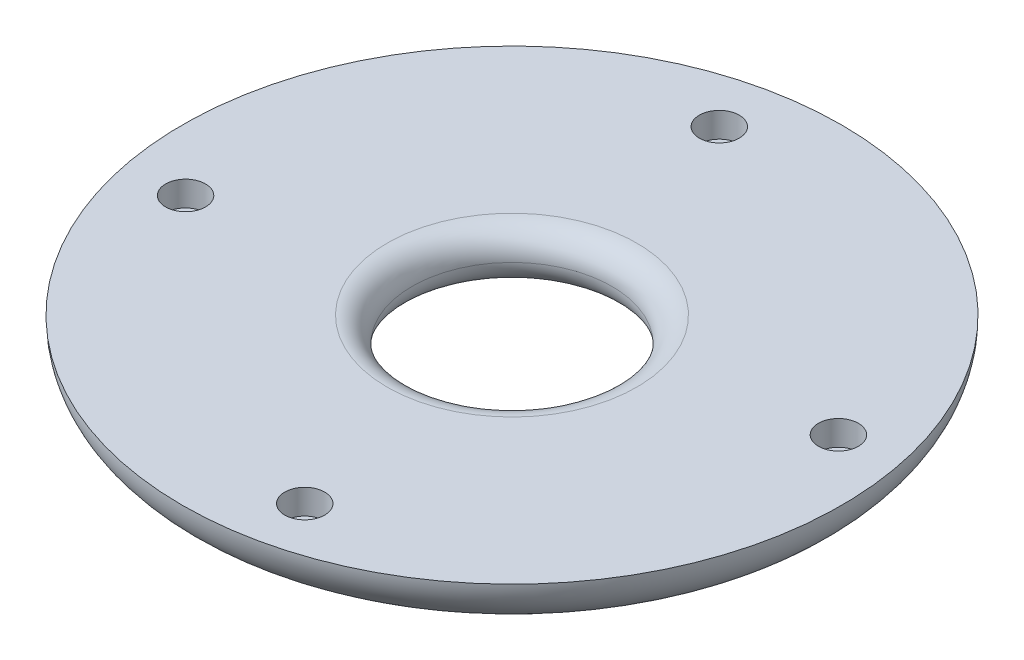
SolidWorks part; units mm, degrees
ref_plane "Front Plane" through (0, 0, 0) normal (0, 0, 1) x (1, 0, 0)
ref_plane "Top Plane" through (0, 0, 0) normal (0, 1, 0) x (1, 0, 0)
ref_plane "Right Plane" through (0, 0, 0) normal (1, 0, 0) x (0, 0, -1)
sketch "Sketch1" plane through (0, 0, 0) normal (0, 1, 0) x (1, 0, 0)
  circle A0 centre (0, 0) radius 33
extrude "Boss-Extrude1" add sketch "Sketch1" along normal blind 5
sketch "Sketch2" plane through (0, 5, 0) normal (0, 1, 0) x (1, 0, 0)
  circle A0 centre (-26.72, -5.9654) radius 2
  circle A1 centre (-5.9654, 26.72) radius 2
  circle A2 centre (26.72, 5.9654) radius 2
  circle A3 centre (5.9654, -26.72) radius 2
  point P11 (0, 0)
  dimension "D1" = 4
extrude "Cut-Extrude1" cut sketch "Sketch2" against normal blind 2.5
fillet "Fillet1" radius 5 1 edges at (0, 0, 33)
sketch "Sketch3" plane through (0, 0, 0) normal (0, -1, 0) x (1, 0, 0)
  line L0 (2, 25) -> (2, 20)
  line L1 (-25, 2) -> (-20, 2)
  line L2 (-25, 2) -> (-25, -2)
  line L3 (-25, -2) -> (-20, -2)
  line L4 (-20, 2) -> (-20, -2)
  line L5 (2, 25) -> (-2, 25)
  line L6 (2, 20) -> (-2, 20)
  line L7 (-2, 25) -> (-2, 20)
  line L8 (25, -2) -> (20, -2)
  line L9 (25, -2) -> (25, 2)
  line L10 (20, -2) -> (20, 2)
  line L11 (25, 2) -> (20, 2)
  line L12 (-2, -25) -> (-2, -20)
  line L13 (-2, -25) -> (2, -25)
  line L14 (-2, -20) -> (2, -20)
  line L15 (2, -25) -> (2, -20)
  circle A0 centre (0, 0) radius 28 construction
  point P22 (0, 0)
  dimension "D1" = 2
  dimension "D2" = 2
  dimension "D3" = 5
  dimension "D4" = 25
  dimension "D5" = 4
extrude "Boss-Extrude2" add sketch "Sketch3" along normal blind 5
fillet "Fillet2" radius 2.5 8 edges at (0, -5, 20) (0, -5, 25) (25, -5, 0) (20, -5, 0) (0, -5, -20) (0, -5, -25) (-25, -5, 0) (-20, -5, 0)
sketch "Sketch4" plane through (0, 0, -2) normal (0, 0, -1) x (-1, 0, 0)
  circle A0 centre (22.5, -2.5) radius 1
  circle A1 centre (-22.3542, -2.5) radius 1
extrude "Cut-Extrude2" cut sketch "Sketch4" against normal blind 5
sketch "Sketch5" plane through (-2, 0, 0) normal (-1, 0, 0) x (0, 0, 1)
  circle A0 centre (22.5, -2.5) radius 1
  circle A1 centre (-22.5, -2.5) radius 1
extrude "Cut-Extrude3" cut sketch "Sketch5" against normal blind 5
sketch "Sketch6" plane through (0, 0, 0) normal (0, -1, 0) x (1, 0, 0)
  circle A0 centre (0, 0) radius 10
extrude "Cut-Extrude4" cut sketch "Sketch6" against normal blind 5
fillet "Fillet3" radius 2.5 2 edges at (0, 5, -10) (0, 0, -10)
